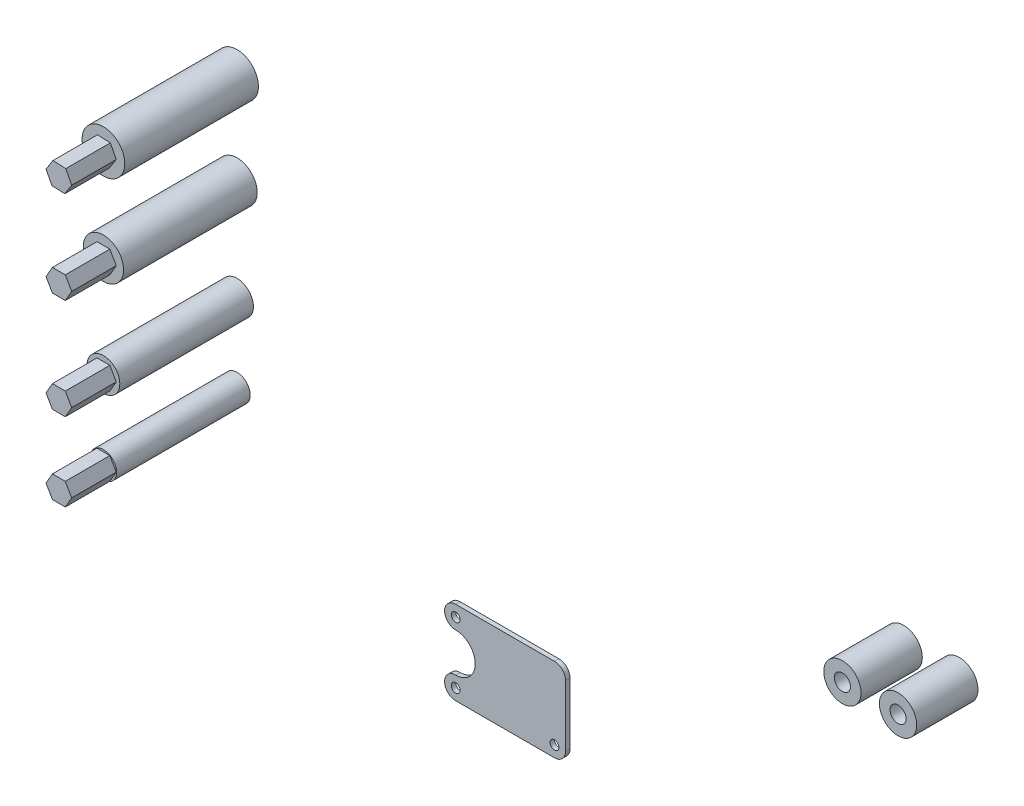
SolidWorks part; units mm, degrees
ref_plane "Front Plane" through (0, 0, 0) normal (0, 0, 1) x (1, 0, 0)
ref_plane "Top Plane" through (0, 0, 0) normal (0, 1, 0) x (1, 0, 0)
ref_plane "Right Plane" through (0, 0, 0) normal (1, 0, 0) x (0, 0, -1)
sketch "Sketch1" plane through (0, 0, 0) normal (0, 0, 1) x (1, 0, 0)
  line L0 (42.5252, 85.2495) -> (55.5016, 85.2495) construction
  line L1 (58.7537, 81.2495) -> (58.7537, 83.2495)
  line L2 (39.0352, 83.2495) -> (39.0252, 83.2495)
  line L3 (39.0252, 79.2495) -> (56.7537, 79.2495)
  line L5 (-0.0481, 105.8254) -> (0.9333, 107.5254)
  line L6 (0.9333, 107.5254) -> (-0.0481, 109.0254)
  line L7 (-0.0481, 109.0254) -> (-2.0111, 109.0254)
  line L8 (-2.0111, 109.0254) -> (-2.9926, 107.5254)
  line L9 (-2.9926, 107.5254) -> (-2.0111, 105.8254)
  line L10 (-2.0111, 105.8254) -> (-0.0481, 105.8254)
  line L11 (0.2405, 119.3642) -> (1.5107, 121.5642)
  line L12 (1.5107, 121.5642) -> (0.2405, 123.5642)
  line L13 (0.2405, 123.5642) -> (-2.2998, 123.5642)
  line L14 (-2.2998, 123.5642) -> (-3.57, 121.5642)
  line L15 (-3.57, 121.5642) -> (-2.2998, 119.3642)
  line L16 (-2.2998, 119.3642) -> (0.2405, 119.3642)
  line L17 (0.5292, 136.9341) -> (2.088, 139.6341)
  line L18 (2.088, 139.6341) -> (0.5292, 142.1341)
  line L19 (0.5292, 142.1341) -> (-2.5885, 142.1341)
  line L20 (-2.5885, 142.1341) -> (-4.1473, 139.6341)
  line L21 (-4.1473, 139.6341) -> (-2.5885, 136.9341)
  line L22 (-2.5885, 136.9341) -> (0.5292, 136.9341)
  line L23 (2.088, 139.6341) -> (2.588, 139.6341) construction
  line L24 (1.5107, 121.5642) -> (1.9107, 121.5642) construction
  line L25 (0.9333, 107.5254) -> (1.3333, 107.5254) construction
  line L26 (42.5252, 86.7395) -> (42.5252, 86.7595)
  line L27 (39.0352, 90.2495) -> (39.0252, 90.2495)
  line L28 (39.0252, 94.2495) -> (51.5016, 94.2495)
  line L29 (53.5016, 87.2495) -> (53.5016, 92.2495)
  line L30 (55.5016, 85.2495) -> (56.7537, 85.2495)
  line L31 (58.7537, 83.2495) -> (58.7537, 92.2495)
  line L32 (56.7537, 94.2495) -> (51.5016, 94.2495)
  line L33 (2.2035, 156.2509) -> (2.8035, 156.2509) construction
  line L34 (2.2035, 156.2509) -> (0.5869, 159.0509)
  line L35 (0.5869, 159.0509) -> (-2.6462, 159.0509)
  line L36 (-2.6462, 159.0509) -> (-4.2628, 156.2509)
  line L37 (-4.2628, 156.2509) -> (-2.6462, 153.4509)
  line L38 (-2.6462, 153.4509) -> (0.5869, 153.4509)
  line L39 (0.5869, 153.4509) -> (2.2035, 156.2509)
  circle A0 centre (39.0252, 81.2495) radius 2
  circle A1 centre (56.7537, 81.2495) radius 2
  circle A2 centre (39.0252, 81.2495) radius 0.8
  circle A3 centre (56.7537, 81.2495) radius 0.8
  arc A4 (58.7537, 92.2495) -> (56.7537, 94.2495) centre (56.7537, 92.2495) ccw
  arc A5 (39.0352, 83.2495) -> (42.5252, 86.7395) centre (39.0352, 86.7395) ccw
  circle A6 centre (-1.0296, 107.5254) radius 1.7 construction
  circle A7 centre (-1.0296, 121.5642) radius 2.2 construction
  circle A8 centre (-1.0296, 139.6341) radius 2.7 construction
  circle A9 centre (-1.0296, 107.5254) radius 2.363
  circle A10 centre (-1.0296, 121.5642) radius 2.9403
  circle A11 centre (-1.0296, 139.6341) radius 3.6177
  circle A12 centre (-1.0296, 139.6341) radius 1.5
  circle A13 centre (-1.0296, 121.5642) radius 1.25
  circle A14 centre (-1.0296, 107.5254) radius 1.05
  circle A15 centre (39.0252, 92.2495) radius 2
  circle A16 centre (39.0252, 92.2495) radius 0.8
  arc A17 (42.5252, 86.7595) -> (39.0352, 90.2495) centre (39.0352, 86.7595) ccw
  circle A18 centre (-1.0296, 156.2509) radius 2.8 construction
  circle A19 centre (-1.0296, 156.2509) radius 3.8332
  circle A20 centre (-1.0296, 156.2509) radius 1.75
  circle B0 centre (78.6519, 127.0575) radius 1.45
  circle B1 centre (78.6519, 127.0575) radius 3.35
  circle B2 centre (78.736, 101.9939) radius 0.85
  circle B3 centre (78.736, 101.9939) radius 2.9
  circle B4 centre (78.736, 114.8621) radius 1.1
  circle B5 centre (78.736, 114.8621) radius 2.7
  circle B6 centre (88.6519, 127.0575) radius 1.45
  circle B7 centre (88.6519, 127.0575) radius 3.35
  circle B8 centre (98.6519, 127.0575) radius 1.45
  circle B9 centre (98.6519, 127.0575) radius 3.35
  circle B10 centre (108.6519, 127.0575) radius 1.45
  circle B11 centre (108.6519, 127.0575) radius 3.35
  circle B12 centre (118.6519, 127.0575) radius 1.45
  circle B13 centre (118.6519, 127.0575) radius 3.35
  circle B14 centre (128.6519, 127.0575) radius 1.45
  circle B15 centre (128.6519, 127.0575) radius 3.35
  circle B16 centre (88.736, 101.9939) radius 0.85
  circle B17 centre (88.736, 101.9939) radius 2.9
  circle B18 centre (98.736, 101.9939) radius 0.85
  circle B19 centre (98.736, 101.9939) radius 2.9
  circle B20 centre (108.736, 101.9939) radius 0.85
  circle B21 centre (108.736, 101.9939) radius 2.9
  circle B22 centre (88.736, 114.8621) radius 1.1
  circle B23 centre (88.736, 114.8621) radius 2.7
  circle B24 centre (76.8787, 139.9756) radius 1.6
  circle B25 centre (76.8787, 139.9756) radius 4
  circle B26 centre (86.8787, 139.9756) radius 1.6
  circle B27 centre (86.8787, 139.9756) radius 4
  dimension "D1" = 4
  dimension "D2" = 1.6
  dimension "D4" = 2
  dimension "D6" = 7
  dimension "D11" = 3
  dimension "D12" = 2.5
  dimension "D13" = 2.1
  dimension "D18" = 4
  dimension "D19" = 1.6
  dimension "D20" = 3.5
  dimension "D21" = 5.6
  dimension "D22" = 0.6
  dimension "D26" = 2
  dimension "D27" = 3.5
  dimension "D5" = 3.49
  dimension "D28" = 3.49
  dimension "D3" = 4
  dimension "D7" = 17.7284
  dimension "D8" = 3.2
  dimension "D9" = 5.2
  dimension "D10" = 4.2
  dimension "D14" = 0.5
  dimension "D15" = 0.4
  dimension "D16" = 0.4
  dimension "D17" = 11
  dimension "D23" = 6
  dimension "D24" = 4
  dimension "D25" = 2
sketch_block_instance "M2.5 spacer-10"
sketch_block "M2.5 spacer" parameters "D1"=2.9, "D3"=6.7, "D4"=2.7, "D2"=4.7
sketch_block_instance "M1.6 spacer-11"
sketch_block "M1.6 spacer" parameters "D1"=1.7, "D3"=5.8, "D4"=1.8, "D2"=3.8
sketch_block_instance "M2 spacer-4"
sketch_block "M2 spacer" parameters "D1"=2.2, "D3"=1, "D4"=2.2, "D2"=3.8
sketch_block_instance "M2.5 spacer-15"
sketch_block_instance "M2.5 spacer-16"
sketch_block_instance "M2.5 spacer-17"
sketch_block_instance "M2.5 spacer-18"
sketch_block_instance "M2.5 spacer-19"
sketch_block_instance "M1.6 spacer-14"
sketch_block_instance "M1.6 spacer-15"
sketch_block_instance "M1.6 spacer-16"
sketch_block_instance "M2 spacer-6"
sketch_block_instance "M3 spacer-1"
sketch_block "M3 spacer" parameters "D1"=3.2, "D2"=8, "D3"=5.6
sketch_block_instance "M3 spacer-2"
extrude "Boss-Extrude1" add sketch "Sketch1" along normal blind 8 contours A11 L22 L21 L20 L19 L18 L17 | A10 L16 L15 L14 L13 L12 L11 | A9 L10 L9 L8 L7 L6 L5 | A19 L39 L38 L37 L36 L35 L34 region at (-3.3258, 107.5254, 0) region at (-3.8868, 121.5642, 0) region at (-4.545, 139.6341, 0) region at (-4.7544, 156.2509, 0)
extrude "Boss-Extrude2" add sketch "Sketch1<3>" along normal blind 16 from surface contours L9 L10 L5 L6 L7 L8 A14 | A9 L10 L9 L8 L7 L6 L5 | A10 L16 L15 L14 L13 L12 L11 | L15 L16 L11 L12 L13 L14 A13 | A11 L22 L21 L20 L19 L18 L17 | L21 L22 L17 L18 L19 L20 A12 | A19 L39 L38 L37 L36 L35 L34 | L38 L39 L34 L35 L36 L37 A20 region at (-1.0296, 105.8761, 0) region at (-1.0296, 119.4301, 0) region at (-1.0296, 137.0153, 0) region at (1.3211, 154.8936, 0) region at (-3.3258, 107.5254, 0) region at (-3.8868, 121.5642, 0) region at (-4.545, 139.6341, 0) region at (-4.7544, 156.2509, 0) starting at face at (-1.0296, 139.5675, 8)
sketch "Sketch1<3>" plane through (0, 0, 0) normal (0, 0, 1) x (1, 0, 0) same geometry as "Sketch1"
sketch "Sketch2" plane through (0, 0, 24) normal (0, 0, 1) x (1, 0, 0)
  circle A0 centre (-1.0296, 156.2509) radius 3.8332 construction
  line B0 (0.1251, 137.6341) -> (1.2798, 139.6341)
  line B1 (1.2798, 139.6341) -> (0.1251, 141.6341)
  line B2 (0.1251, 141.6341) -> (-2.1843, 141.6341)
  line B3 (-2.1843, 141.6341) -> (-3.339, 139.6341)
  line B4 (-3.339, 139.6341) -> (-2.1843, 137.6341)
  line B5 (-2.1843, 137.6341) -> (0.1251, 137.6341)
  circle B6 centre (-1.0296, 139.6341) radius 2 construction
  line B7 (0.1251, 119.5642) -> (1.2798, 121.5642)
  line B8 (1.2798, 121.5642) -> (0.1251, 123.5642)
  line B9 (0.1251, 123.5642) -> (-2.1843, 123.5642)
  line B10 (-2.1843, 123.5642) -> (-3.339, 121.5642)
  line B11 (-3.339, 121.5642) -> (-2.1843, 119.5642)
  line B12 (-2.1843, 119.5642) -> (0.1251, 119.5642)
  circle B13 centre (-1.0296, 121.5642) radius 2 construction
  line B14 (0.1251, 105.5254) -> (1.2798, 107.5254)
  line B15 (1.2798, 107.5254) -> (0.1251, 109.5254)
  line B16 (0.1251, 109.5254) -> (-2.1843, 109.5254)
  line B17 (-2.1843, 109.5254) -> (-3.339, 107.5254)
  line B18 (-3.339, 107.5254) -> (-2.1843, 105.5254)
  line B19 (-2.1843, 105.5254) -> (0.1251, 105.5254)
  circle B20 centre (-1.0296, 107.5254) radius 2 construction
  line B21 (0.0317, 154.1998) -> (1.2773, 156.1444)
  line B22 (1.2773, 156.1444) -> (0.216, 158.1955)
  line B23 (0.216, 158.1955) -> (-2.0909, 158.302)
  line B24 (-2.0909, 158.302) -> (-3.3366, 156.3573)
  line B25 (-3.3366, 156.3573) -> (-2.2753, 154.3062)
  line B26 (-2.2753, 154.3062) -> (0.0317, 154.1998)
  circle B27 centre (-1.0296, 156.2509) radius 2 construction
sketch_block_instance "T4-hex-1"
sketch_block "T4-hex" parameters "D1"=4
sketch_block_instance "T4-hex-2"
sketch_block_instance "T4-hex-3"
sketch_block_instance "T4-hex-4"
extrude "Boss-Extrude3" add sketch "Sketch2" along normal blind 8
chamfer "Chamfer1" distance 1 angle 60 1 edges at (0.0204, 107.5254, 24) first distance on face at (0.0204, 107.5254, 24)
chamfer "Chamfer2" distance 1.2 angle 60 1 edges at (0.2204, 121.5642, 24) first distance on face at (0.2204, 121.5642, 24)
chamfer "Chamfer3" distance 1.4 angle 60 1 edges at (0.4704, 139.6341, 24) first distance on face at (0.4704, 139.6341, 24)
chamfer "Chamfer4" distance 1.6 angle 60 1 edges at (0.7204, 156.2509, 24) first distance on face at (0.7204, 156.2509, 24)
extrude "Boss-Extrude4" add sketch "Sketch1<5>" along normal blind 0.8 separate body contours L30 L29 L28 A15 L27 A17 L26 A5 L2 A0 L3 A1 L1 | A0 A2 | A1 A3 | A15 A16 region at (49.5289, 87.0262, 0) region at (58.1279, 79.8753, 0) region at (37.0818, 81.2495, 0) region at (40.3994, 93.6237, 0)
sketch "Sketch1<5>" plane through (0, 0, 0) normal (0, 0, 1) x (1, 0, 0) same geometry as "Sketch1"
extrude "Boss-Extrude5" add sketch "Sketch1<7>" along normal blind 11 separate body contours B15 B14 | B13 B12 region at (115.3966, 127.0575, 0) region at (125.3966, 127.0575, 0)
sketch "Sketch1<7>" plane through (0, 0, 0) normal (0, 0, 1) x (1, 0, 0) same geometry as "Sketch1"
